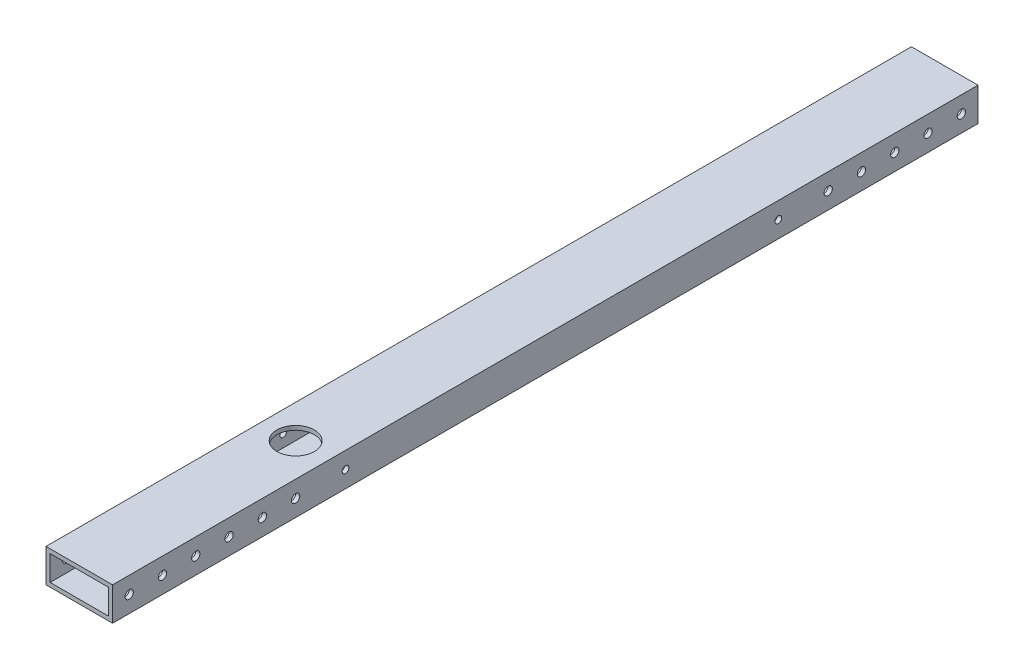
SolidWorks part; units mm, degrees
material "6061 Alloy"
ref_plane "Front Plane" through (0, 0, 0) normal (0, 0, 1) x (1, 0, 0)
ref_plane "Top Plane" through (0, 0, 0) normal (0, 1, 0) x (1, 0, 0)
ref_plane "Right Plane" through (0, 0, 0) normal (1, 0, 0) x (0, 0, -1)
sketch "Sketch1" plane through (0, 0, 0) normal (0, 0, 1) x (1, 0, 0)
  line L0 (-22.225, 9.525) -> (22.225, 9.525)
  line L2 (-25.4, 12.7) -> (25.4, 12.7)
  line L3 (-25.4, 12.7) -> (-25.4, -12.7)
  line L4 (-25.4, -12.7) -> (25.4, -12.7)
  line L5 (25.4, 12.7) -> (25.4, -12.7)
  line L10 (22.225, 9.525) -> (22.225, -9.525)
  line L11 (-22.225, -9.525) -> (22.225, -9.525)
  line L12 (-22.225, 9.525) -> (-22.225, -9.525)
  point P12 (0, 12.7)
  point P14 (25.4, 0)
  dimension "Wall Thickness" = 3.175
  dimension "Outside Width" = 50.8
  dimension "Outside Height" = 25.4
  dimension "Inside Height" = 19.05
  dimension "Inside Width" = 44.45
sketch "Sketch2" plane through (0, 0, 0) normal (1, 0, 0) x (0, 0, -1)
  line L0 (330.2, 0) -> (-330.2, 0)
  point P4 (0, 0)
  point P7 (-330.2, 0)
  point P10 (330.2, 0)
  dimension "Length" = 660.4
sketch "Sketch3" plane through (0, 0, 0) normal (0, 0, 1) x (1, 0, 0)
  line L21 (25.4, 12.7) -> (-25.4, 12.7)
  line L22 (25.4, -12.7) -> (25.4, 12.7)
  line L23 (-25.4, -12.7) -> (25.4, -12.7)
  line L24 (-25.4, 12.7) -> (-25.4, -12.7)
  line L25 (25.4, 12.7) -> (-25.4, 12.7)
  line L26 (25.4, -12.7) -> (25.4, 12.7)
  line L27 (-25.4, -12.7) -> (25.4, -12.7)
  line L28 (-25.4, 12.7) -> (-25.4, -12.7)
  line L29 (22.225, 9.525) -> (-22.225, 9.525)
  line L30 (22.225, -9.525) -> (22.225, 9.525)
  line L31 (-22.225, -9.525) -> (22.225, -9.525)
  line L32 (-22.225, 9.525) -> (-22.225, -9.525)
  line L33 (22.225, 9.525) -> (-22.225, 9.525)
  line L34 (22.225, -9.525) -> (22.225, 9.525)
  line L35 (-22.225, -9.525) -> (22.225, -9.525)
  line L36 (-22.225, 9.525) -> (-22.225, -9.525)
  dimension "D1" = 0
  dimension "D2" = 0
extrude "Boss-Extrude1" add sketch "Sketch3" along normal up to vertex (330.2 mm away) and the other way up to vertex (330.2 mm away) up to point (0, 0, 330.2) other way up to point (0, 0, -330.2)
sketch "Drawing Reference" plane through (0, 0, 0) normal (1, 0, 0) x (0, 0, -1)
  line L0 (-330.2, 0) -> (330.2, 0) construction
  line L1 (0, -12.7) -> (0, 12.7) construction
  line L2 (-330.2, -12.7) -> (330.2, -12.7) construction
  line L5 (-330.2, 12.7) -> (330.2, 12.7) construction
  point P7 (-293.624, 0)
  point P8 (293.624, 0)
  dimension "D1" = 36.576
sketch "Sketch5" plane through (25.4, 0, 0) normal (1, 0, 0) x (0, 0, -1)
  line L2 (-266.7, 0) -> (-241.3, 0)
  line L3 (-241.3, 0) -> (-215.9, 0)
  line L4 (-215.9, 0) -> (-190.5, 0)
  line L5 (-317.5, 0) -> (-330.2, 0)
  line L6 (-330.2, -12.7) -> (-330.2, 12.7) construction
  line L7 (-317.5, 0) -> (-292.1, 0)
  line L8 (-292.1, 0) -> (-266.7, 0)
sketch "Sketch8" plane through (25.4, 0, 0) normal (1, 0, 0) x (0, 0, -1)
  line L0 (330.2, 0) -> (292.1, 0)
  line L1 (330.2, -12.7) -> (330.2, 12.7) construction
  line L2 (292.1, 0) -> (266.7, 0)
  line L3 (266.7, 0) -> (241.3, 0)
  line L4 (241.3, 0) -> (215.9, 0)
  line L5 (330.2, 0) -> (317.5, 0)
hole_wizard "1/4 (0.25) Diameter Hole3" positions "Sketch12" profile "Sketch13" hole size "1/4" standard "ANSI Inch" end condition through all
sketch "Sketch12" plane through (-25.4, 0, 0) normal (-1, 0, 0) x (0, 0, 1)
  point P4 (-317.5, 0)
sketch "Sketch13" plane through (-25.4, 0, -317.5) normal (0, 1, 0) x (0, 0, 1)
  line L0 (0, 0) -> (0, 50.8)
  line L1 (0, 50.8) -> (3.175, 50.8)
  line L2 (3.175, 50.8) -> (3.175, 0)
  line L5 (3.175, 0) -> (0, 0)
  line L11 (0, -6.35) -> (0, 107.95) construction
  dimension "Thru Hole Dia." = 6.35
  dimension "Thru Hole Depth" = 50.8
hole_wizard "1/4 (0.25) Diameter Hole4" positions "Sketch14" profile "Sketch15" hole size "1/4" standard "ANSI Inch" end condition through all
sketch "Sketch14" plane through (-25.4, 0, 0) normal (-1, 0, 0) x (0, 0, 1)
  point P0 (292.1, 0)
  point P3 (317.5, 0)
sketch "Sketch15" plane through (-25.4, 0, 292.1) normal (0, 1, 0) x (0, 0, 1)
  line L0 (0, 0) -> (0, 50.8)
  line L1 (0, 50.8) -> (3.175, 50.8)
  line L2 (3.175, 50.8) -> (3.175, 0)
  line L5 (3.175, 0) -> (0, 0)
  line L11 (0, -6.35) -> (0, 107.95) construction
  dimension "Thru Hole Dia." = 6.35
  dimension "Thru Hole Depth" = 50.8
hole_wizard "1/4 (0.25) Diameter Hole5" positions "Sketch17" profile "Sketch18" hole size "1/4" standard "ANSI Inch" end condition through all
sketch "Sketch17" plane through (25.4, 0, 0) normal (1, 0, 0) x (0, 0, -1)
  point P0 (292.1, 0)
  point P3 (266.7, 0)
sketch "Sketch18" plane through (25.4, 0, -292.1) normal (0, 1, 0) x (0, 0, -1)
  line L0 (0, 0) -> (0, 50.8)
  line L1 (0, 50.8) -> (3.175, 50.8)
  line L2 (3.175, 50.8) -> (3.175, 0)
  line L5 (3.175, 0) -> (0, 0)
  line L11 (0, -6.35) -> (0, 107.95) construction
  dimension "Thru Hole Dia." = 6.35
  dimension "Thru Hole Depth" = 50.8
hole_wizard "1/4 (0.25) Diameter Hole6" positions "Sketch19" profile "Sketch20" hole size "1/4" standard "ANSI Inch" end condition through all
sketch "Sketch19" plane through (25.4, 0, 0) normal (1, 0, 0) x (0, 0, -1)
  point P0 (215.9, 0)
  point P3 (241.3, 0)
sketch "Sketch20" plane through (25.4, 0, -215.9) normal (0, 1, 0) x (0, 0, -1)
  line L0 (0, 0) -> (0, 50.8)
  line L1 (0, 50.8) -> (3.175, 50.8)
  line L2 (3.175, 50.8) -> (3.175, 0)
  line L5 (3.175, 0) -> (0, 0)
  line L11 (0, -6.35) -> (0, 107.95) construction
  dimension "Thru Hole Dia." = 6.35
  dimension "Thru Hole Depth" = 50.8
hole_wizard "1/4 (0.25) Diameter Hole7" positions "Sketch21" profile "Sketch22" hole size "1/4" standard "ANSI Inch" end condition through all
sketch "Sketch21" plane through (25.4, 0, 0) normal (1, 0, 0) x (0, 0, -1)
  point P0 (-190.5, 0)
  point P3 (-215.9, 0)
sketch "Sketch22" plane through (25.4, 0, 190.5) normal (0, 1, 0) x (0, 0, -1)
  line L0 (0, 0) -> (0, 50.8)
  line L1 (0, 50.8) -> (3.175, 50.8)
  line L2 (3.175, 50.8) -> (3.175, 0)
  line L5 (3.175, 0) -> (0, 0)
  line L11 (0, -6.35) -> (0, 107.95) construction
  dimension "Thru Hole Dia." = 6.35
  dimension "Thru Hole Depth" = 50.8
hole_wizard "1/4 (0.25) Diameter Hole8" positions "Sketch23" profile "Sketch24" hole size "1/4" standard "ANSI Inch" end condition through all
sketch "Sketch23" plane through (25.4, 0, 0) normal (1, 0, 0) x (0, 0, -1)
  point P0 (-266.7, 0)
  point P3 (-241.3, 0)
sketch "Sketch24" plane through (25.4, 0, 266.7) normal (0, 1, 0) x (0, 0, -1)
  line L0 (0, 0) -> (0, 50.8)
  line L1 (0, 50.8) -> (3.175, 50.8)
  line L2 (3.175, 50.8) -> (3.175, 0)
  line L5 (3.175, 0) -> (0, 0)
  line L11 (0, -6.35) -> (0, 107.95) construction
  dimension "Thru Hole Dia." = 6.35
  dimension "Thru Hole Depth" = 50.8
sketch "Sketch25" plane through (25.4, 0, 0) normal (1, 0, 0) x (0, 0, -1)
  line L0 (-190.5, 0) -> (-152.4, 0)
  line L1 (215.9, 0) -> (177.8, 0)
hole_wizard "13/64 (0.20313) Diameter Hole1" positions "Sketch26" profile "Sketch27" hole size "13/64" standard "ANSI Inch" end condition through all
sketch "Sketch26" plane through (25.4, 0, 0) normal (1, 0, 0) x (0, 0, -1)
  point P0 (-152.4, 0)
  point P3 (177.8, 0)
sketch "Sketch27" plane through (25.4, 0, 152.4) normal (0, 1, 0) x (0, 0, -1)
  line L0 (0, 0) -> (0, 50.8)
  line L1 (0, 50.8) -> (2.5798, 50.8)
  line L2 (2.5798, 50.8) -> (2.5798, 0)
  line L5 (2.5798, 0) -> (0, 0)
  line L11 (0, -6.35) -> (0, 107.95) construction
  dimension "Thru Hole Dia." = 5.1595
  dimension "Thru Hole Depth" = 50.8
sketch "Sketch30" plane through (-25.4, 0, 0) normal (-1, 0, 0) x (0, 0, 1)
  point P0 (-128.5875, 0)
  point P1 (-103.1875, 0)
  point P2 (77.7875, 0)
  point P3 (103.1875, 0)
hole_wizard "1/2 (0.5) Diameter Hole1" positions "Sketch33" profile "Sketch34" hole size "1/2" standard "ANSI Inch"
sketch "Sketch33" plane through (-25.4, 0, 0) normal (-1, 0, 0) x (0, 0, 1)
  point P0 (-128.5875, 0)
  point P3 (-103.1875, 0)
  point P7 (77.7875, 0)
  point P10 (103.1875, 0)
sketch "Sketch34" plane through (-25.4, 0, -128.5875) normal (0, 1, 0) x (0, 0, 1)
  line L0 (0, 0) -> (0, 10.1655)
  line L1 (0, 10.1655) -> (6.35, 6.35)
  line L2 (6.35, 6.35) -> (6.35, 0)
  line L5 (6.35, 0) -> (0, 0)
  line L10 (0, 10.1655) -> (-6.35, 6.35) construction
  line L11 (0, -6.35) -> (0, 107.95) construction
  dimension "Hole Dia." = 12.7
  dimension "Hole Depth" = 6.35
  dimension "Drill Angle" = 118
sketch "Sketch36" plane through (0, -12.7, 0) normal (0, -1, 0) x (1, 0, 0)
  line L0 (-25.4, 165.1081) -> (25.4, 165.1081) construction
  line L1 (-25.4, 330.2) -> (-25.4, -330.2) construction
  line L2 (25.4, 330.2) -> (25.4, -330.2) construction
  line L3 (0, 165.1081) -> (7.7911, 138.8057) construction
  line L4 (-25.4, 128.9741) -> (575.1111, 306.8536) construction
  line L5 (7.7911, 138.8057) -> (-2.7276, 135.69) construction
  circle A0 centre (0, 165.1081) radius 14.2875
  dimension "D2" = 28.575
  dimension "D1" = 27.432
extrude "Cut-Extrude1" cut sketch "Sketch36" against normal through all
equation "\"D1@Drawing Reference\"=\"Outside Width@Sketch1\" * 0.72"
